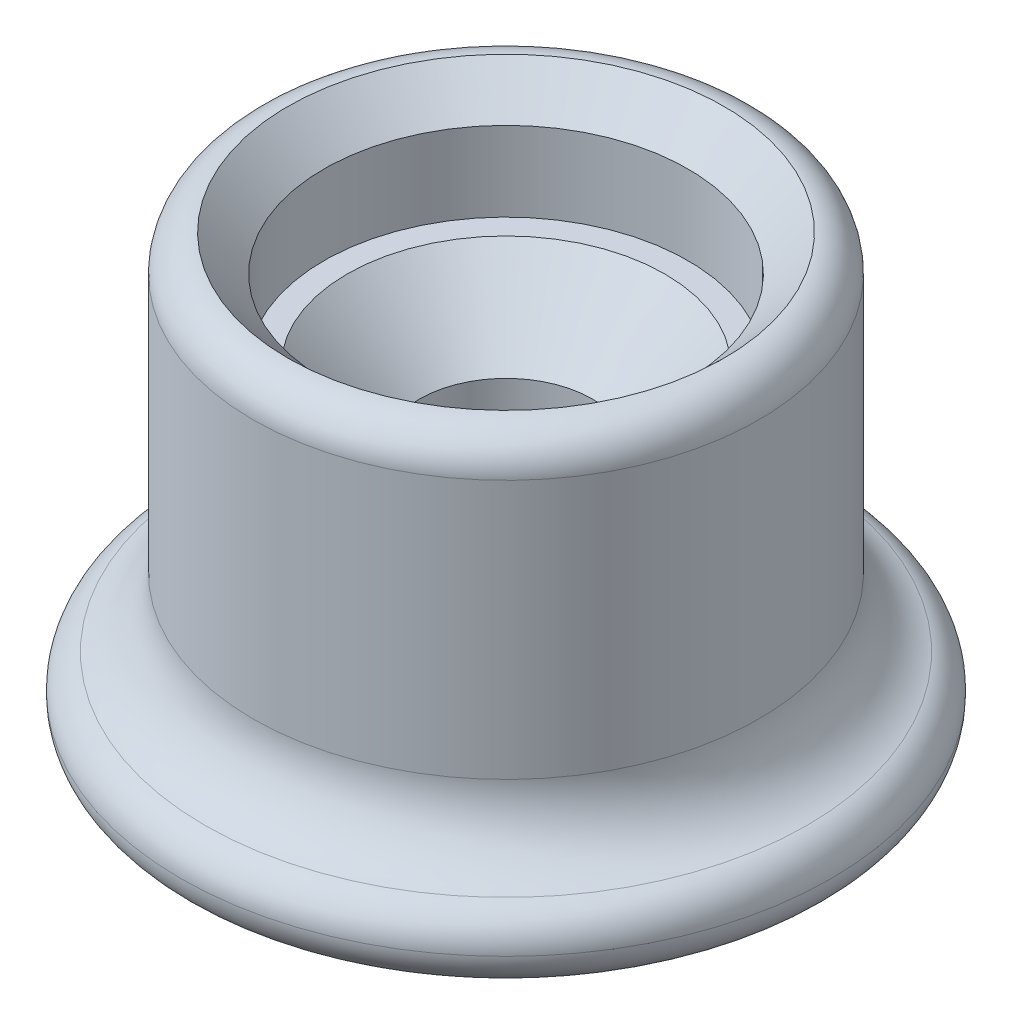
SolidWorks part; units mm, degrees
ref_plane "Front Plane" through (0, 0, 0) normal (0, 0, 1) x (1, 0, 0)
ref_plane "Top Plane" through (0, 0, 0) normal (0, 1, 0) x (1, 0, 0)
ref_plane "Right Plane" through (0, 0, 0) normal (1, 0, 0) x (0, 0, -1)
sketch "Sketch4" plane through (0, 0, 0) normal (0, 1, 0) x (1, 0, 0)
  circle A0 centre (0, 0) radius 5.5562
  circle A1 centre (0, 0) radius 1.905
  dimension "D1" = 11.1125
  dimension "D2" = 3.81
extrude "Boss-Extrude3" add sketch "Sketch4" along normal blind 9.525
sketch "Sketch5" plane through (0, 0, 0) normal (0, -1, 0) x (-1, 0, 0)
  circle A1 centre (0, 0) radius 1.905 construction
  circle A2 centre (0, 0) radius 7.1437
  circle A3 centre (0, 0) radius 7.1437
  circle A4 centre (0, 0) radius 1.905
  dimension "D1" = 1.5875
extrude "Boss-Extrude4" add sketch "Sketch5" against normal blind 1.5875
fillet "Fillet4" radius 0.7937 3 edges at (0, 0, -7.1437) (0, 1.5875, -7.1437) (0, 9.525, 5.5562)
fillet "Fillet5" radius 1.5875 1 edges at (0, 1.5875, -5.5562)
sketch "Sketch6" plane through (0, 9.525, 0) normal (0, 1, 0) x (1, 0, 0)
  circle A0 centre (0, 0) radius 4.0005
  dimension "D1" = 8.001
extrude "Cut-Extrude1" cut sketch "Sketch6" against normal blind 2.54
chamfer "Chamfer1" distance 0.7937 angle 45 1 edges at (0, 9.525, 4.0005)
chamfer "Chamfer2" distance 1.5875 angle 45 1 edges at (0, 6.985, 1.905)
equation "\".0625n\"=0.375"
